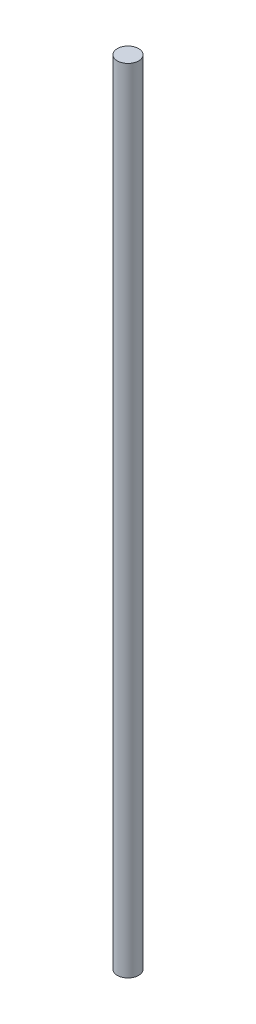
SolidWorks part; units mm, degrees
ref_plane "Front Plane" through (0, 0, 0) normal (0, 0, 1) x (1, 0, 0)
ref_plane "Top Plane" through (0, 0, 0) normal (0, 1, 0) x (1, 0, 0)
ref_plane "Right Plane" through (0, 0, 0) normal (1, 0, 0) x (0, 0, -1)
sketch "Sketch1" plane through (0, 0, 0) normal (0, 1, 0) x (1, 0, 0)
  circle A0 centre (0, 0) radius 5
  dimension "D1" = 10
extrude "Boss-Extrude1" add sketch "Sketch1" along normal blind 371.36
